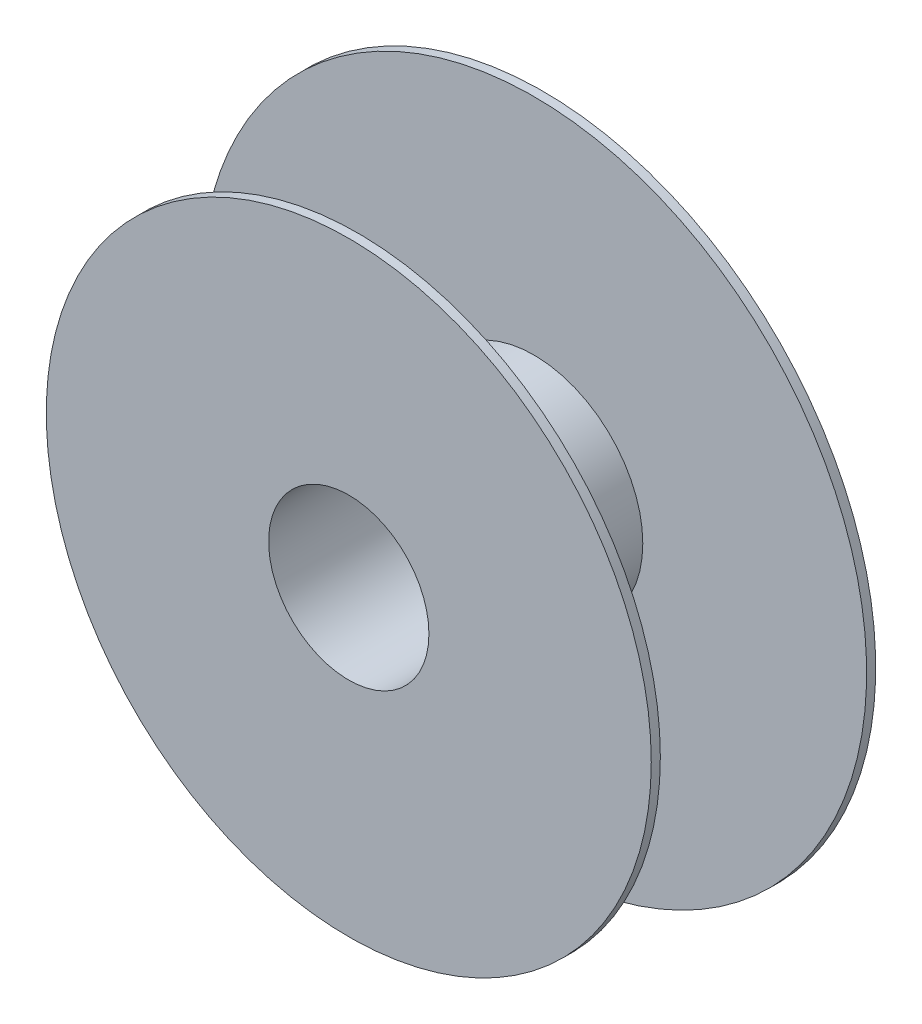
SolidWorks part; units mm, degrees
ref_plane "Спереди" through (0, 0, 0) normal (0, 0, 1) x (1, 0, 0)
ref_plane "Сверху" through (0, 0, 0) normal (0, 1, 0) x (1, 0, 0)
ref_plane "Справа" through (0, 0, 0) normal (1, 0, 0) x (0, 0, -1)
sketch "Sketch1" plane through (0, 0, 0) normal (0, 0, 1) x (1, 0, 0)
  circle A0 centre (0, 0) radius 26.5
  circle A1 centre (0, 0) radius 36
  dimension "D1" = 53
  dimension "D2" = 72
extrude "Extrude1" add sketch "Sketch1" along normal blind 29.1 and the other way blind 29.1
sketch "Sketch2" plane through (0, 0, 29.1) normal (0, 0, 1) x (1, 0, 0)
  circle A0 centre (0, 0) radius 100
  circle A3 centre (0, 0) radius 26.5 construction
  circle A4 centre (0, 0) radius 26.5
  dimension "D1" = 200
extrude "Extrude4" add sketch "Sketch2" along normal blind 3
sketch "Sketch4" plane through (0, 0, -29.1) normal (0, 0, -1) x (-1, 0, 0)
  circle A0 centre (0, 0) radius 110
  circle A1 centre (0, 0) radius 26.5 construction
  circle A2 centre (0, 0) radius 26.5
  dimension "D1" = 220
extrude "Extrude5" add sketch "Sketch4" along normal blind 3
